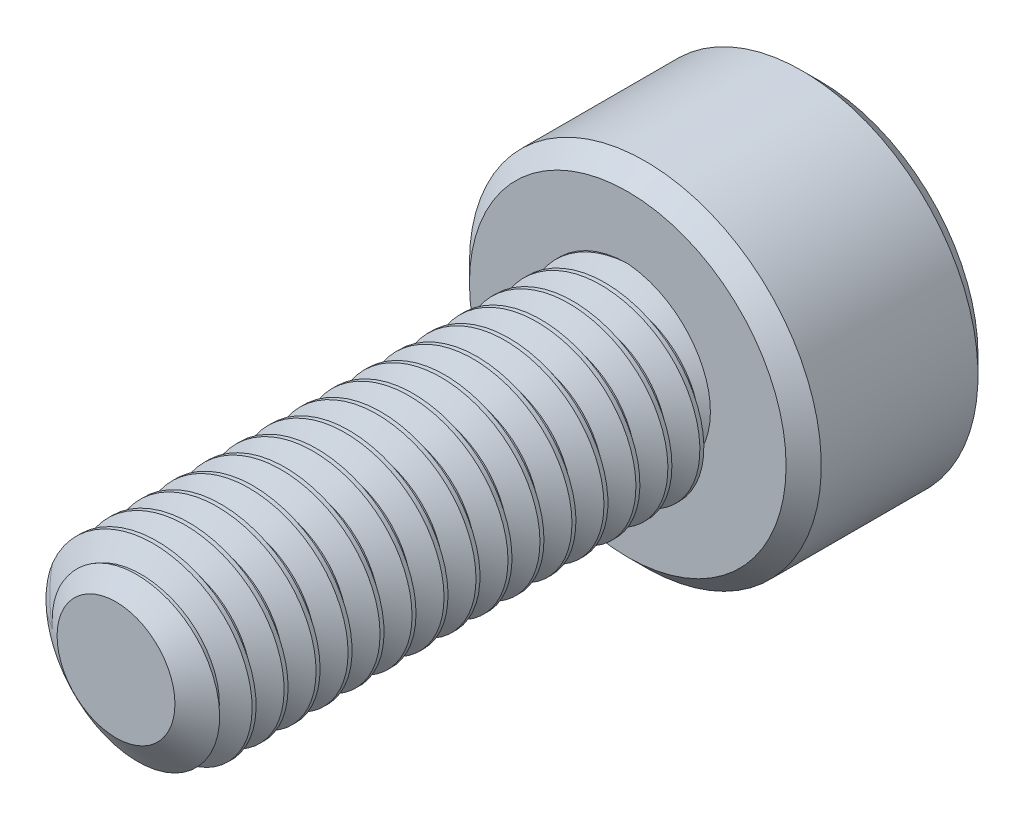
SolidWorks part; units mm, degrees
other "DetailItem1"
ref_plane "Front Plane" through (0, 0, 0) normal (0, 0, 1) x (1, 0, 0)
ref_plane "Top Plane" through (0, 0, 0) normal (0, 1, 0) x (1, 0, 0)
ref_plane "Right Plane" through (0, 0, 0) normal (1, 0, 0) x (0, 0, -1)
sketch "Sketch1" plane through (0, 0, 0) normal (0, 0, 1) x (1, 0, 0)
  circle A0 centre (0, 0) radius 1.5
  dimension "OD" = 3
extrude "Extrude1" add sketch "Sketch1" against normal blind 8
sketch "Sketch2" plane through (0, 0, 0) normal (0, 0, 1) x (1, 0, 0)
  circle A0 centre (0, 0) radius 1.5 construction
  circle A1 centre (0, 0) radius 1.5
curve "Helix/Spiral1" pitch 0.5 height 8.5 radius 1.5 centre (0, 0, 0) axis (0, 0, -1) start towards (0, 1, 0) parameters "pitch"=0.5
sketch "Sketch3" plane through (0, 0, 0) normal (1, 0, 0) x (0, 0, -1)
  line L0 (-0.4375, 1.5) -> (-0.25, 1.1752)
  line L1 (-0.25, 1.1752) -> (-0.1875, 1.1752)
  line L2 (-0.1875, 1.1752) -> (0, 1.5)
  line L3 (-0.4375, 1.5) -> (0, 1.5)
  line L4 (-0.2187, 1.5) -> (-0.2188, 1.1752) construction
  line L5 (-0.3438, 1.3376) -> (-0.0938, 1.3376) construction
  line L6 (0, 1.5) -> (0, -1.5) construction
  dimension "D1" = 0.0625
  dimension "D2" = 0.25
  dimension "D3" = 60
sweep "Cut-Sweep1" cut profiles "Sketch3" path "Helix/Spiral1"
sketch "Sketch4" plane through (0, 0, 0) normal (1, 0, 0) x (0, 0, -1)
  line L0 (0.4053, 1.5) -> (0, 0.9212)
  line L1 (0, 0.9212) -> (0, 1.5)
  line L2 (0.4053, 1.5) -> (0, 1.5)
  line L3 (-0.4375, 1.5) -> (0, 1.5) construction
  line L4 (0, 0) -> (7.0209, 0) construction
  dimension "D1" = 55
  dimension "D2" = 0.254
revolve "Cut-Revolve1" cut sketch "Sketch4" angle 360 about L4
sketch "Sketch6" plane through (0, 0, -8) normal (0, 0, -1) x (-1, 0, 0)
  circle A0 centre (0, 0) radius 2.75
  dimension "head dia" = 5.5
extrude "Extrude2" add sketch "Sketch6" along normal blind 3
sketch "Sketch7" plane through (0, 0, -11) normal (0, 0, -1) x (-1, 0, 0)
  line L1 (0, 1.4434) -> (-1.25, 0.7217)
  line L2 (-1.25, 0.7217) -> (-1.25, -0.7217)
  line L3 (-1.25, -0.7217) -> (0, -1.4434)
  line L4 (0, -1.4434) -> (1.25, -0.7217)
  line L5 (1.25, -0.7217) -> (1.25, 0.7217)
  line L6 (1.25, 0.7217) -> (0, 1.4434)
  circle A0 centre (0, 0) radius 1.25 construction
  dimension "hex dia" = 2.5
extrude "Cut-Extrude1" cut sketch "Sketch7" against normal blind 1.875
sketch "Sketch8" plane through (0, 0, -11) normal (0, 0, -1) x (-1, 0, 0)
  circle A0 centre (0, 0) radius 1.4434
extrude "Cut-Extrude2" cut sketch "Sketch8" against normal through all draft 45
chamfer "Chamfer1" distance 0.275 angle 45 2 edges at (-2.75, 0, -11) (-2.75, 0, -8)
sketch "Sketch10" plane through (0, 0, -8) normal (0, 0, 1) x (1, 0, 0)
  circle A1 centre (0, 0) radius 1.5
  circle A2 centre (0, 0) radius 1.5
  dimension "D1" = 0
ref_plane "Plane1" through (0, 0, 0) normal (0, 0, 1) x (1, 0, 0)
extrude "partial thread" [suppressed] add sketch "Sketch10" along normal up to surface (4 mm away) separate body up to plane "Plane1"
chamfer "Chamfer2" [suppressed] distance 0.06 angle 45
combine bodies "Combine1" [suppressed] operation type add bodies to combine 107 108
sketch "Sketch9" plane through (0, 0, 0) normal (1, 0, 0) x (0, 0, -1)
  line L0 (0, 1.5) -> (0, -1.5) construction
  line L1 (1.25, 1.5) -> (1.25, -1.5) construction
  dimension "D1" = 1.25
  dimension "D4" = 0.635
  dimension "D5" = 0.3302
equation "\"D3@Helix/Spiral1\" = \"screw length@Extrude1\"+\"pitch@Helix/Spiral1\""
equation "\"D1@Sketch3\" = \"pitch@Helix/Spiral1\"*.125"
equation "\"D2@Sketch3\" = \"pitch@Helix/Spiral1\"*.5"
equation "\"D1@Cut-Extrude1\" = \"hex dia@Sketch7\"*.75"
equation "\"D1@Chamfer1\" = \"head dia@Sketch6\"*.05"
equation "\"D1@Sketch9\" = \"pitch@Helix/Spiral1\"*2.5"
equation "\"D1@Chamfer2\"=\"OD@Sketch1\"*.02"
